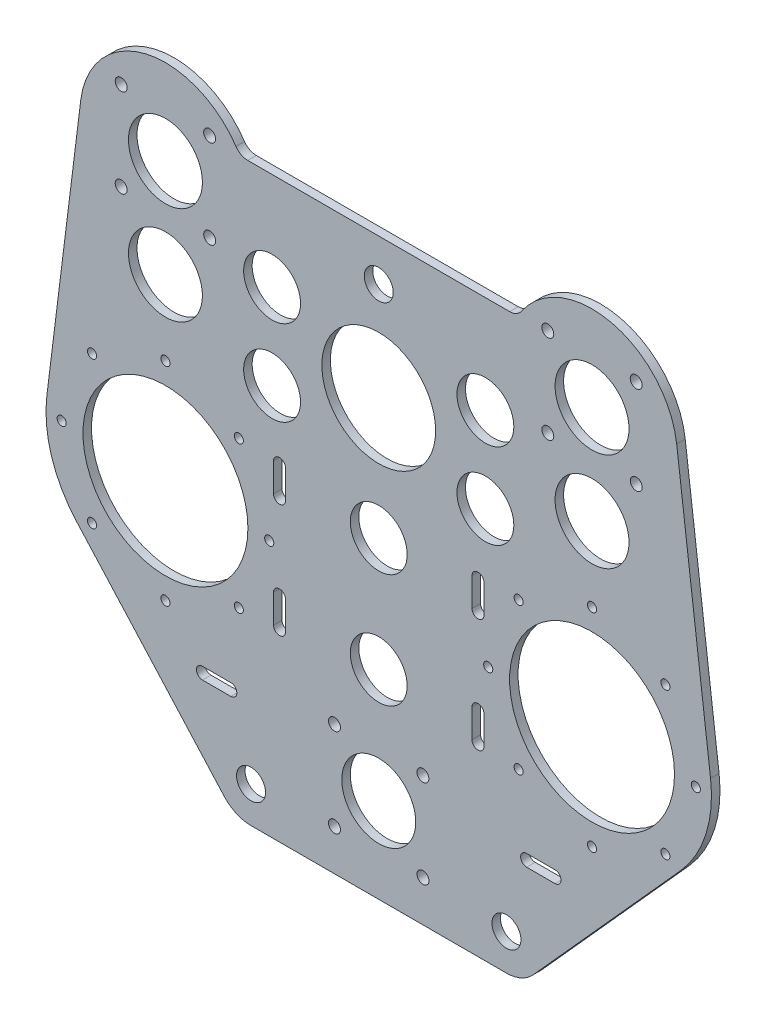
SolidWorks part; units mm, degrees
material "Thornel Mat VMA"
ref_plane "Front Plane" through (0, 0, 0) normal (0, 0, 1) x (1, 0, 0)
ref_plane "Top Plane" through (0, 0, 0) normal (0, 1, 0) x (1, 0, 0)
ref_plane "Right Plane" through (0, 0, 0) normal (1, 0, 0) x (0, 0, -1)
sketch "Model" plane through (0, 0, 0) normal (0, 0, 1) x (1, 0, 0)
  line L0 (-37, 5) -> (-37, -5)
  line L1 (-32.8, 5) -> (-32.8, -5)
  line L2 (-37, -35) -> (-37, -45)
  line L3 (-32.8, -35) -> (-32.8, -45)
  line L4 (-44.9, -110) -> (0, -110)
  line L5 (37, 5) -> (37, -5)
  line L6 (32.8, 5) -> (32.8, -5)
  line L7 (37, -35) -> (37, -45)
  line L8 (32.8, -35) -> (32.8, -45)
  line L9 (44.9, -110) -> (0, -110)
  line L10 (-62, -70) -> (-52, -70)
  line L11 (-62, -74.2) -> (-52, -74.2)
  line L12 (62, -70) -> (52, -70)
  line L13 (62, -74.2) -> (52, -74.2)
  line L14 (-106.2292, -48.0845) -> (-54.3252, -105.8002)
  line L15 (106.2292, -48.0845) -> (54.3252, -105.8002)
  line L16 (-46.0542, 92) -> (0, 92)
  line L17 (46.0542, 92) -> (0, 92)
  line L18 (-104.7711, 81.0231) -> (-116.6795, -14.8214)
  line L19 (104.7711, 81.0231) -> (116.6795, -14.8214)
  circle A0 centre (0, -80) radius 13
  arc A1 (-32.8, 5) -> (-37, 5) centre (-34.9, 5) ccw
  arc A2 (-37, -5) -> (-32.8, -5) centre (-34.9, -5) ccw
  arc A3 (-32.8, -35) -> (-37, -35) centre (-34.9, -35) ccw
  arc A4 (-37, -45) -> (-32.8, -45) centre (-34.9, -45) ccw
  circle A5 centre (-44.9, -97.3241) radius 5.1
  arc A6 (37, 5) -> (32.8, 5) centre (34.9, 5) ccw
  arc A7 (32.8, -5) -> (37, -5) centre (34.9, -5) ccw
  arc A8 (37, -35) -> (32.8, -35) centre (34.9, -35) ccw
  arc A9 (32.8, -45) -> (37, -45) centre (34.9, -45) ccw
  circle A10 centre (44.9, -97.3241) radius 5.1
  arc A11 (-62, -70) -> (-62, -74.2) centre (-62, -72.1) ccw
  arc A12 (-52, -74.2) -> (-52, -70) centre (-52, -72.1) ccw
  arc A13 (62, -74.2) -> (62, -70) centre (62, -72.1) ccw
  arc A14 (52, -70) -> (52, -74.2) centre (52, -72.1) ccw
  circle A15 centre (0, 77.3241) radius 5.1
  circle A16 centre (0, 0) radius 10
  circle A17 centre (0, -40) radius 10
  circle A18 centre (0, 42.6759) radius 20
  circle A19 centre (-37.5, 57.6759) radius 10
  circle A20 centre (-37.5, 27.6759) radius 10
  circle A21 centre (37.5, 57.6759) radius 10
  circle A22 centre (37.5, 27.6759) radius 10
  arc A23 (-54.3252, -105.8002) -> (-44.9, -110) centre (-44.9, -97.3241) ccw
  arc A24 (44.9, -110) -> (54.3252, -105.8002) centre (44.9, -97.3241) ccw
  circle A25 centre (-75, -20) radius 29
  circle A26 centre (-75, 16.5) radius 1.6
  circle A27 centre (-100.8094, 5.8094) radius 1.6
  circle A28 centre (-49.1906, 5.8094) radius 1.6
  circle A29 centre (-38.5, -20) radius 1.6
  circle A30 centre (-49.1906, -45.8094) radius 1.6
  circle A31 centre (-75, -56.5) radius 1.6
  circle A32 centre (-100.8094, -45.8094) radius 1.6
  circle A33 centre (-111.5, -20) radius 1.6
  circle A34 centre (75, -20) radius 29
  circle A35 centre (75, 16.5) radius 1.6
  circle A36 centre (49.1906, 5.8094) radius 1.6
  circle A37 centre (100.8094, 5.8094) radius 1.6
  circle A38 centre (111.5, -20) radius 1.6
  circle A39 centre (100.8094, -45.8094) radius 1.6
  circle A40 centre (75, -56.5) radius 1.6
  circle A41 centre (49.1906, -45.8094) radius 1.6
  circle A42 centre (38.5, -20) radius 1.6
  circle A43 centre (-75, 77.3241) radius 13
  arc A44 (-50.1893, 94.1892) -> (-104.7711, 81.0231) centre (-75, 77.3241) ccw
  arc A45 (-50.1893, 94.1892) -> (-46.0542, 92) centre (-46.0542, 97) ccw
  circle A46 centre (75, 77.3241) radius 13
  arc A47 (104.7711, 81.0231) -> (50.1893, 94.1892) centre (75, 77.3241) ccw
  arc A48 (46.0542, 92) -> (50.1893, 94.1892) centre (46.0542, 97) ccw
  arc A49 (-116.6795, -14.8214) -> (-106.2292, -48.0845) centre (-75, -20) ccw
  arc A50 (106.2292, -48.0845) -> (116.6795, -14.8214) centre (75, -20) ccw
  circle A51 centre (-75, 42.8013) radius 13
  circle A52 centre (75, 42.6759) radius 13
  circle A53 centre (-59.4676, 92.8565) radius 2.1
  circle A54 centre (-90.5563, 92.8805) radius 2.1
  circle A55 centre (-90.5563, 61.7678) radius 2.1
  circle A56 centre (-59.4437, 61.7678) radius 2.1
  circle A57 centre (90.5324, 92.8565) radius 2.1
  circle A58 centre (59.4437, 92.8805) radius 2.1
  circle A59 centre (59.4437, 61.7678) radius 2.1
  circle A60 centre (90.5563, 61.7678) radius 2.1
  circle A61 centre (15.5324, -64.4676) radius 2.1
  circle A62 centre (-15.5563, -64.4437) radius 2.1
  circle A63 centre (-15.5563, -95.5563) radius 2.1
  circle A64 centre (15.5563, -95.5563) radius 2.1
extrude "Boss-Extrude1" add sketch "Model" along normal blind 3
